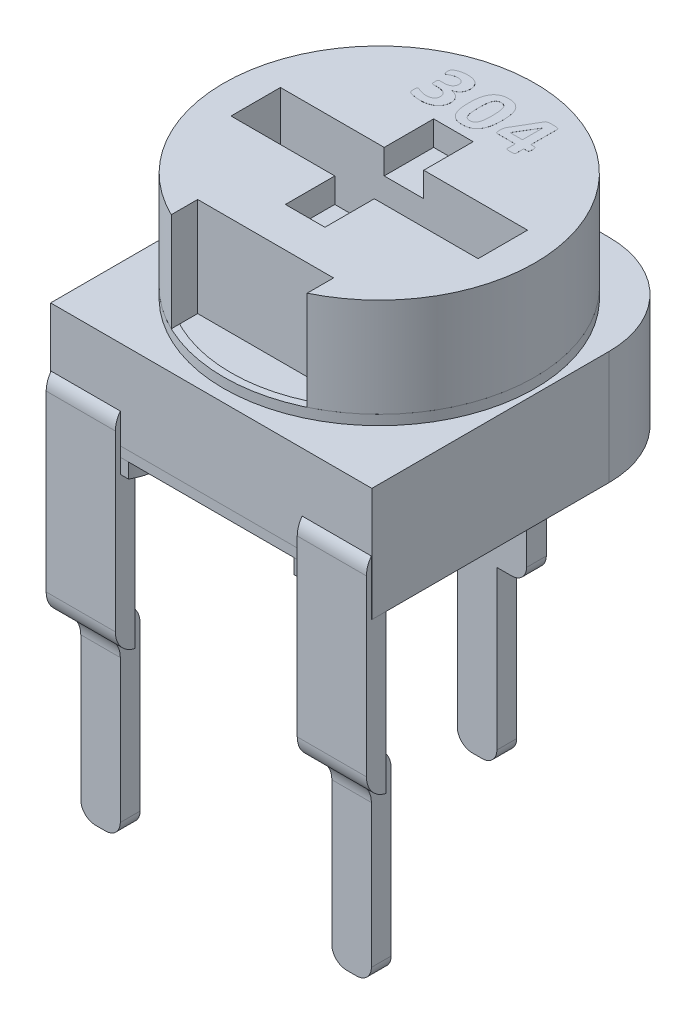
SolidWorks part; units mm, degrees
material "ABS"
ref_plane "Front Plane" through (0, 0, 0) normal (0, 0, 1) x (1, 0, 0)
ref_plane "Top Plane" through (0, 0, 0) normal (0, 1, 0) x (1, 0, 0)
ref_plane "Right Plane" through (0, 0, 0) normal (1, 0, 0) x (0, 0, -1)
sketch "Sketch1" plane through (0, 0, 0) normal (0, 1, 0) x (1, 0, 0)
  line L0 (0, 3.15) -> (0, -3.15) construction
  line L1 (0, 3.15) -> (0, 3.4) construction
  line L2 (0, -3.15) -> (0, -3.4) construction
  line L3 (-3.15, 0) -> (3.15, 0) construction
  line L4 (3.15, 0) -> (3.25, 0) construction
  line L5 (-3.15, 0) -> (-3.25, 0) construction
  line L6 (-3.25, -3.4) -> (3.25, -3.4)
  line L7 (-3.25, -3.4) -> (-3.25, 3.4)
  line L8 (-3.25, 3.4) -> (3.25, 3.4)
  line L9 (3.25, 3.4) -> (3.25, -3.4)
  circle A0 centre (0, 0) radius 3.15 construction
  dimension "D1" = 6.3
  dimension "D2" = 6.8
  dimension "D3" = 6.5
extrude "Boss-Extrude1" add sketch "Sketch1" along normal blind 2.3
sketch "Sketch2" plane through (0, 2.3, 0) normal (0, 1, 0) x (1, 0, 0)
  circle A0 centre (0, 0) radius 3.15 construction
  circle A1 centre (0, 0) radius 3.15
extrude "Boss-Extrude2" add sketch "Sketch2" along normal blind 0.2
fillet "Fillet1" radius 2 2 edges at (3.25, 1.15, -3.4) (-3.25, 1.15, -3.4)
sketch "Sketch3" plane through (0, 0, 0) normal (0, -1, 0) x (1, 0, 0)
  line L0 (0, 0) -> (0, -2.5) construction
  line L1 (-1.75, -2.5) -> (1.75, -2.5)
  line L6 (-2.25, -2) -> (-2.25, 2)
  line L7 (2.25, -2) -> (2.25, 2)
  line L8 (-2.25, 2) -> (-3, 2)
  line L9 (-3, 2) -> (-3, 3.4)
  line L10 (-3.25, 3.4) -> (3.25, 3.4) construction
  line L11 (2.25, 2) -> (3, 2)
  line L12 (3, 2) -> (3, 3.4)
  line L13 (3, 3.4) -> (-3, 3.4)
  line L14 (0, 0) -> (0, 3.4) construction
  arc A0 (-1.75, -2.5) -> (-2.25, -2) centre (-1.75, -2) cw
  arc A1 (1.75, -2.5) -> (2.25, -2) centre (1.75, -2) ccw
  point P20 (2.25, -2.5)
  dimension "D6" = 0.5
  dimension "D1" = 4.5
  dimension "D2" = 2.5
  dimension "D3" = 4.5
  dimension "D4" = 1.4
  dimension "D5" = 6
extrude "Cut-Extrude1" cut sketch "Sketch3" against normal blind 0.5
sketch "Sketch4" plane through (0, 0.5, 0) normal (0, -1, 0) x (1, 0, 0)
  line L8 (-3, 2) -> (-2.25, 2)
  line L9 (-2.25, 2) -> (-2.25, -2)
  line L10 (-1.75, -2.5) -> (1.75, -2.5)
  line L11 (2.25, -2) -> (2.25, 2)
  line L12 (2.25, 2) -> (3, 2)
  line L13 (3, 2) -> (3, 3.4)
  line L14 (3, 3.4) -> (-3, 3.4)
  line L15 (-3, 3.4) -> (-3, 2)
  line L16 (-3, 2) -> (-2.25, 2)
  line L17 (-2.25, 2) -> (-2.25, -2)
  line L18 (-1.75, -2.5) -> (1.75, -2.5)
  line L19 (2.25, -2) -> (2.25, 2)
  line L20 (2.25, 2) -> (3, 2)
  line L21 (3, 2) -> (3, 3.4)
  line L22 (3, 3.4) -> (-3, 3.4)
  line L23 (-3, 3.4) -> (-3, 2)
  arc A2 (-2.25, -2) -> (-1.75, -2.5) centre (-1.75, -2) ccw
  arc A3 (1.75, -2.5) -> (2.25, -2) centre (1.75, -2) ccw
  arc A4 (-2.25, -2) -> (-1.75, -2.5) centre (-1.75, -2) ccw
  arc A5 (1.75, -2.5) -> (2.25, -2) centre (1.75, -2) ccw
  dimension "D1" = 0
extrude "Boss-Extrude3" add sketch "Sketch4" along normal blind 0.2 separate body
sketch "Sketch5" plane through (0, 0.3, 0) normal (0, -1, 0) x (1, 0, 0)
  line L0 (0, 3.4) -> (0, 2.9) construction
  line L1 (3, 3.4) -> (-3, 3.4) construction
  line L2 (0, 2.9) -> (0, -2.18) construction
  line L3 (-2.54, 2.9) -> (2.54, 2.9) construction
  circle A0 centre (2.54, 2.9) radius 1
  circle A1 centre (-2.54, 2.9) radius 1
  circle A2 centre (0, -2.18) radius 1
  dimension "D2" = 5.08
  dimension "D4" = 2
  dimension "D1" = 0.5
  dimension "D3" = 5.08
extrude "Boss-Extrude4" add sketch "Sketch5" along normal up to surface (0.3 mm away) up to face at (0, 0, 0.1228)
sketch "Sketch6" plane through (0, 0.3, 0) normal (0, 1, 0) x (1, 0, 0)
  line L0 (-3.25, -3.4) -> (-3.25, -1)
  line L1 (-3.25, 1.4) -> (-3.25, -3.4) construction
  line L2 (-3.25, -1) -> (-4.35, -1)
  line L3 (-4.35, -1) -> (-4.35, -4.5)
  line L4 (-4.35, -4.5) -> (4.35, -4.5)
  line L5 (4.35, -4.5) -> (4.35, -1)
  line L6 (4.35, -1) -> (3.25, -1)
  line L7 (3.25, -3.4) -> (3.25, 1.4) construction
  line L8 (-3.25, -3.4) -> (3.25, -3.4)
  line L9 (3.25, -3.4) -> (3.25, -1)
  line L10 (0, 0) -> (0, -3.4) construction
  line L11 (0, -3.4) -> (0, -4.5) construction
  dimension "D1" = 3.5
extrude "Cut-Extrude2" cut sketch "Sketch6" against normal up to surface (0.3 mm away) up to face at (0, 0, -0.817)
sketch "Sketch8" plane through (0, 0.3, 0) normal (0, -1, 0) x (1, 0, 0)
  line L1 (-0.4, -1.98) -> (0.4, -1.98)
  line L2 (-0.4, -1.98) -> (-0.4, -2.38)
  line L3 (-0.4, -2.38) -> (0.4, -2.38)
  line L4 (0.4, -1.98) -> (0.4, -2.38)
  line L5 (-0.4, -1.98) -> (0.4, -2.38) construction
  line L6 (-0.4, -2.38) -> (0.4, -1.98) construction
  line L7 (-2.94, 3.1) -> (-2.14, 3.1)
  line L8 (-2.94, 3.1) -> (-2.94, 2.7)
  line L9 (-2.94, 2.7) -> (-2.14, 2.7)
  line L10 (-2.14, 3.1) -> (-2.14, 2.7)
  line L11 (-2.94, 3.1) -> (-2.14, 2.7) construction
  line L12 (-2.94, 2.7) -> (-2.14, 3.1) construction
  line L13 (2.94, 3.1) -> (2.14, 3.1)
  line L14 (2.94, 3.1) -> (2.94, 2.7)
  line L15 (2.94, 2.7) -> (2.14, 2.7)
  line L16 (2.14, 3.1) -> (2.14, 2.7)
  line L17 (2.94, 3.1) -> (2.14, 2.7) construction
  line L18 (2.94, 2.7) -> (2.14, 3.1) construction
  point P0 (0, -2.18)
  point P5 (-2.54, 2.9)
  point P11 (2.54, 2.9)
  dimension "D1" = 0.4
  dimension "D2" = 0.8
extrude "Boss-Extrude5" add sketch "Sketch8" along normal blind 7
sketch "Sketch9" plane through (0, 0.3, 0) normal (0, -1, 0) x (1, 0, 0)
  line L4 (0, -1.98) -> (0, -2.38) construction
  line L5 (0.4, -1.98) -> (-0.4, -1.98) construction
  line L6 (-0.4, -2.38) -> (0.4, -2.38) construction
  line L8 (-1, -1.98) -> (1, -1.98)
  line L9 (-1, -1.98) -> (-1, -2.38)
  line L10 (-1, -2.38) -> (1, -2.38)
  line L11 (1, -1.98) -> (1, -2.38)
  line L12 (-1, -1.98) -> (1, -2.38) construction
  line L13 (-1, -2.38) -> (1, -1.98) construction
  point P14 (0, -2.18)
  dimension "D1" = 2
extrude "Boss-Extrude6" add sketch "Sketch9" along normal blind 3.5
sketch "Sketch10" plane through (0, 0.3, 0) normal (0, -1, 0) x (1, 0, 0)
  line L0 (-2.54, 3.1) -> (-2.54, 3.5) construction
  line L1 (-2.14, 3.1) -> (-2.94, 3.1) construction
  line L2 (2.54, 3.1) -> (2.54, 3.5) construction
  line L3 (2.94, 3.1) -> (2.14, 3.1) construction
  line L4 (-2.94, 3.1) -> (-2.94, 2.7) construction
  line L5 (-3.24, 3.5) -> (-1.84, 3.5)
  line L6 (-3.24, 3.5) -> (-3.24, 3.1)
  line L7 (-3.24, 3.1) -> (-1.84, 3.1)
  line L8 (-1.84, 3.5) -> (-1.84, 3.1)
  line L10 (1.84, 3.5) -> (3.24, 3.5)
  line L11 (1.84, 3.5) -> (1.84, 3.1)
  line L12 (1.84, 3.1) -> (3.24, 3.1)
  line L13 (3.24, 3.5) -> (3.24, 3.1)
  dimension "D1" = 1.4
extrude "Boss-Extrude7" add sketch "Sketch10" along normal blind 3.5 and the other way blind 1
fillet "Fillet2" radius 0.5 2 edges at (2.54, 1.3, 3.5) (-2.54, 1.3, 3.5)
sketch "Sketch11" plane through (0, 0, 0) normal (1, 0, 0) x (0, 0, -1)
  line L0 (-3.4, 0) -> (1.4, 0) construction
  line L1 (-3.1, -2.8) -> (-2.7, -2.8)
  line L2 (-3.1, -2.8) -> (-3.1, 0)
  line L3 (-3.1, 0) -> (-2.7, 0)
  line L4 (-2.7, -2.8) -> (-2.7, 0)
  line L5 (-2.7, -6.7) -> (-2.7, 0.3) construction
  line L6 (-3.1, -2.8) -> (-3.1, -3.2) construction
extrude "Cut-Extrude3" cut sketch "Sketch11" against normal through all both and the other way through all
fillet "Fillet3" radius 0.5 4 edges at (-2.54, -2.8, 3.1) (2.54, -2.8, 3.1) (-2.54, -3.2, 3.5) (2.54, -3.2, 3.5)
fillet "Fillet4" radius 0.5 4 edges at (2.54, -2.8, 2.7) (-2.54, -2.8, 2.7) (2.54, -3.2, 3.1) (-2.54, -3.2, 3.1)
fillet "Fillet5" radius 0.3 12 edges at (-1, -3.2, -2.18) (1, -3.2, -2.18) (-0.4, -6.7, -2.18) (0.4, -6.7, -2.18) (2.14, -6.7, 2.9) (2.94, -6.7, 2.9) (-2.94, -6.7, 2.9) (-2.14, -6.7, 2.9) (-2.14, -2.7551, 3.1) (-2.94, -2.7551, 3.1) (2.14, -2.7551, 3.1) (2.94, -2.7551, 3.1)
sketch "Sketch12" plane through (0, 0.3, 0) normal (0, -1, 0) x (1, 0, 0)
  circle A0 centre (0, 0) radius 2
  circle A1 centre (0, 0) radius 1.5
  dimension "D1" = 4
  dimension "D2" = 3
extrude "Boss-Extrude8" add sketch "Sketch12" along normal blind 0.15
sketch "Sketch15" plane through (0, 2.5, 0) normal (0, 1, 0) x (1, 0, 0)
  circle A0 centre (0, 0) radius 3
  dimension "D1" = 6
extrude "Cut-Extrude4" cut sketch "Sketch15" against normal blind 0.5
sketch "Sketch14" plane through (0, 2.5, 0) normal (0, 1, 0) x (1, 0, 0)
  circle A1 centre (0, 0) radius 3.15
  circle A2 centre (0, 0) radius 3.15
  dimension "D1" = 0
extrude "Boss-Extrude9" add sketch "Sketch14" along normal blind 2 separate body
sketch "Set Angle of Knob" plane through (0, 4.5, 0) normal (0, 1, 0) x (1, 0, 0)
  line L0 (0, 0) -> (0, -3.15) construction
  line L1 (-2.5, 0) -> (2.5, 0) construction
  line L2 (-2.5, 0.5) -> (-2.5, -0.5)
  line L3 (2.5, 0.5) -> (2.5, -0.5)
  line L4 (-2.5, 0.5) -> (-0.4, 0.5)
  line L5 (-2.5, -0.5) -> (-0.4, -0.5)
  line L6 (0, 0) -> (0, -1.5) construction
  line L7 (0, 0) -> (0, 1.5) construction
  line L8 (0, 1.5) -> (0, 3.15) construction
  line L9 (0.4, 1.5) -> (-0.4, 1.5)
  line L10 (0.4, 1.5) -> (0.4, 0.5)
  line L11 (-0.4, 1.5) -> (-0.4, 0.5)
  line L12 (0.4, 0.5) -> (2.5, 0.5)
  line L13 (-0.4, -1.5) -> (0.4, -1.5)
  line L14 (-0.4, -1.5) -> (-0.4, -0.5)
  line L15 (0.4, -1.5) -> (0.4, -0.5)
  line L16 (0.4, -0.5) -> (2.5, -0.5)
  line L17 (0, -1.5) -> (0, -2.3) construction
  line L18 (-1.375, -2.3) -> (1.375, -2.3)
  line L19 (-1.375, -2.3) -> (-1.375, -3.8)
  line L20 (1.375, -2.3) -> (1.375, -3.8)
  line L21 (-1.375, -3.8) -> (1.375, -3.8)
  line L22 (-1, 0.25) -> (1, 0.25) construction
  line L23 (-1, 0.25) -> (-1, -0.25) construction
  line L24 (-1, -0.25) -> (1, -0.25) construction
  line L25 (1, -0.25) -> (1, 0.25) construction
  circle A0 centre (0, 0) radius 3.15 construction
  circle A1 centre (0, 0) radius 3.15 construction
  point P32 (0, 0.25)
  dimension "D1" = 1
  dimension "D2" = 0.8
  dimension "D3" = 1.5
  dimension "D4" = 5
  dimension "D5" = 90
  dimension "D6" = 2.75
  dimension "D7" = 1.5
  dimension "D8" = 1.8
  dimension "D9" = 0.25
  dimension "D10" = 0.25
  dimension "D11" = 2
extrude "TURN KNOB" cut sketch "Set Angle of Knob" against normal blind 2.3
sketch "Sketch17" plane through (0, 2, 0) normal (0, 1, 0) x (1, 0, 0)
  line L0 (-0.4, -1.5) -> (0.4, -1.5)
  line L1 (0.4, -1.5) -> (0.4, -0.5)
  line L2 (0.4, 1.5) -> (-0.4, 1.5)
  line L3 (-0.4, 1.5) -> (-0.4, 0.5)
  line L4 (-0.4, 0.5) -> (0.4, 0.5)
  line L5 (-0.4, -0.5) -> (0.4, -0.5)
  line L6 (-0.4, -0.5) -> (-0.4, -1.5)
  line L7 (0.4, 0.5) -> (0.4, 1.5)
extrude "Boss-Extrude10" add sketch "Sketch17" along normal blind 2
sketch "Sketch20" plane through (0, 2, 0) normal (0, 1, 0) x (1, 0, 0)
  line L0 (-1, 0.25) -> (1, 0.25) construction
  line L1 (-1, 0.25) -> (1, 0.25)
  line L2 (-1, -0.25) -> (1, -0.25) construction
  line L3 (-1, -0.25) -> (1, -0.25)
  line L4 (-1, 0.25) -> (-1, -0.25) construction
  line L5 (-1, 0.25) -> (-1, -0.25)
  line L6 (1, -0.25) -> (1, 0.25) construction
  line L7 (1, -0.25) -> (1, 0.25)
extrude "Cut-Extrude6" cut sketch "Sketch20" against normal blind 0.5
fillet "Fillet6" radius 0.2 2 edges at (1, 2, 0) (-1, 2, 0)
sketch "See Code in Properties" plane through (0, 4.5, 0) normal (0, 1, 0) x (1, 0, 0)
  line L0 (0, 1.5) -> (0, 1.7) construction
  line L1 (0.4, 1.5) -> (-0.4, 1.5) construction
  line L2 (0, 1.5) -> (0, 3.15) construction
  line L3 (-1.5, 1.7) -> (1.5, 1.7) construction
  text T0 "304" font "Calibri" height 0.9
  dimension "D1" = 0.2
  dimension "D2" = 3
extrude "Code Number" add sketch "See Code in Properties" along normal blind 0.001
